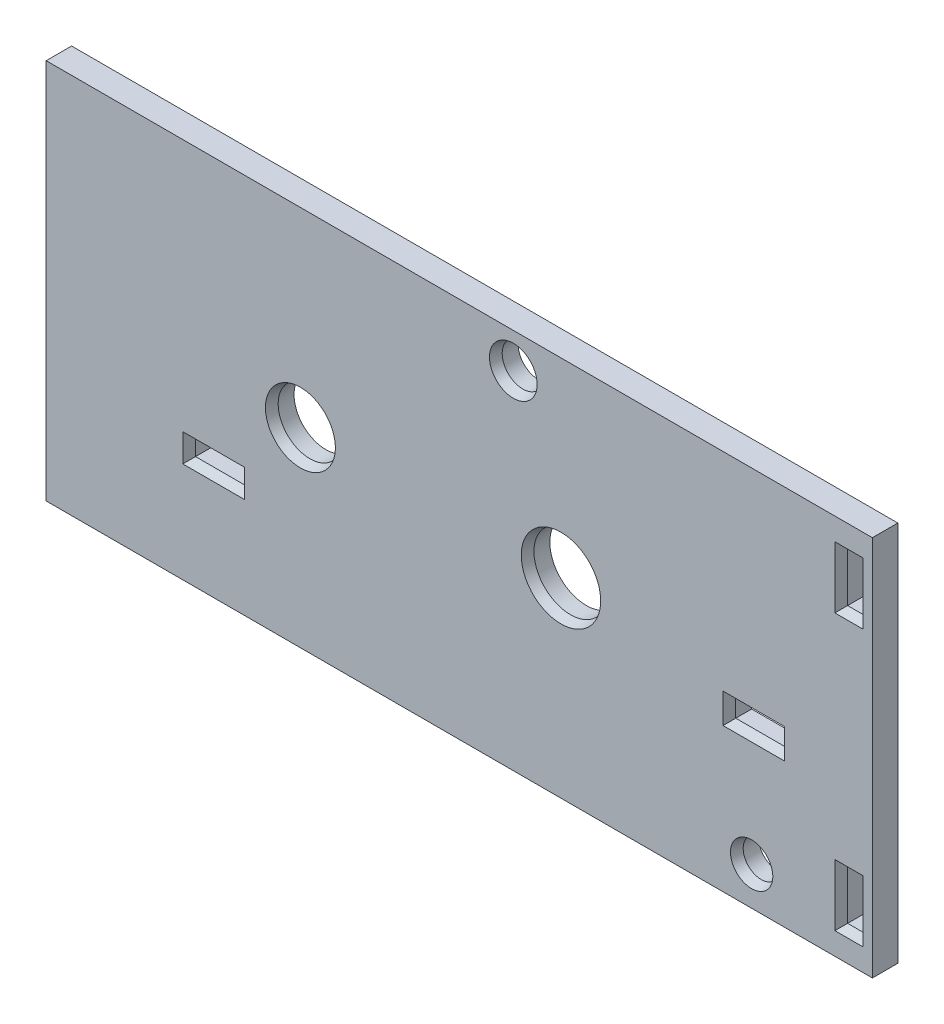
SolidWorks part; units mm, degrees
ref_plane "Front Plane" through (0, 0, 0) normal (0, 0, 1) x (1, 0, 0)
ref_plane "Top Plane" through (0, 0, 0) normal (0, 1, 0) x (1, 0, 0)
ref_plane "Right Plane" through (0, 0, 0) normal (1, 0, 0) x (0, 0, -1)
sketch "Sketch1" plane through (0, 0, 0) normal (0, 0, 1) x (1, 0, 0)
  line L0 (-55.3, -10.3) -> (-55.3, -13.7)
  line L1 (-86, -30) -> (44, -30)
  line L2 (-86, -30) -> (-86, 30)
  line L3 (-86, 30) -> (44, 30)
  line L4 (44, -30) -> (44, 30)
  line L5 (-64, -10.3) -> (-55.3, -10.3)
  line L6 (-64, -10.3) -> (-64, -13.7)
  line L7 (-64, -13.7) -> (-55.3, -13.7)
  line L13 (29.7, -5) -> (21, -5) construction
  line L14 (-55.3, -12) -> (-64, -12) construction
  line L15 (-59.65, -10.3) -> (-59.65, -13.7) construction
  line L16 (40.3, 26) -> (40.3, 17.3) construction
  line L17 (38.6, 26) -> (42, 26)
  line L18 (38.6, 26) -> (38.6, 17.3)
  line L19 (38.6, 17.3) -> (42, 17.3)
  line L20 (42, 26) -> (42, 17.3)
  line L21 (38.6, -17.3) -> (42, -17.3)
  line L22 (38.6, -17.3) -> (38.6, -26)
  line L23 (38.6, -26) -> (42, -26)
  line L24 (42, -17.3) -> (42, -26)
  line L25 (42, 21.65) -> (38.6, 21.65) construction
  line L26 (40.3, -17.3) -> (40.3, -26) construction
  line L27 (42, -21.65) -> (38.6, -21.65) construction
  line L28 (21, -3.15) -> (29.7, -3.15)
  line L29 (21, -3.15) -> (21, -6.85)
  line L30 (21, -6.85) -> (29.7, -6.85)
  line L31 (29.7, -3.15) -> (29.7, -6.85)
  line L32 (25.35, -6.85) -> (25.35, -3.15) construction
  circle A2 centre (-46, 0) radius 5
  circle A3 centre (-12.5, 24.5) radius 3.25
  circle A4 centre (25, -24) radius 2.83
  circle A5 centre (-5, 0) radius 5.75
  point P1 (0, 0)
  point P24 (-86, 0)
  dimension "D10" = 6.5
  dimension "D14" = 5.66
  dimension "D21" = 10
  dimension "D22" = 11.5
  dimension "D2" = 60
  dimension "D4" = 130
  dimension "D6" = 8.7
  dimension "D8" = 3.4
  dimension "D12" = 111
  dimension "D19" = 24.5
  dimension "D13" = 24
  dimension "D5" = 40
  dimension "D7" = 33.5
  dimension "D9" = 7.5
  dimension "D11" = 26.35
  dimension "D15" = 126.3
  dimension "D17" = 21.65
  dimension "D18" = 21.65
  dimension "D16" = 85
  dimension "D3" = 5
  dimension "D20" = 12
extrude "Boss-Extrude1" add sketch "Sketch1" along normal mid plane 4
sketch "Sketch2" plane through (0, 0, 2) normal (0, 0, 1) x (1, 0, 0)
  line L0 (40.3, 26) -> (40.3, 17.3) construction
  line L1 (42, 21.65) -> (38.6, 21.65) construction
  line L2 (40.3, -17.3) -> (40.3, -26) construction
  line L3 (42, -17.3) -> (38.6, -17.3) construction
  line L4 (38.6, -26) -> (42, -26) construction
  line L5 (38.6, -21.65) -> (42, -21.65) construction
  line L6 (38.6, -17.3) -> (38.6, -26) construction
  line L7 (42, -26) -> (42, -17.3) construction
sketch "Sketch4" plane through (0, 0, -2) normal (0, 0, -1) x (-1, 0, 0)
  line L0 (59.65, -10.3) -> (59.65, -13.7) construction
  line L1 (55.3, -12) -> (64, -12) construction
  line L2 (-29.7, -5) -> (-21, -5) construction
  line L3 (-29.7, -6.85) -> (-29.7, -3.15) construction
  line L4 (-21, -3.15) -> (-21, -6.85) construction
  line L5 (-25.35, -3.15) -> (-25.35, -6.85) construction
  line L6 (-29.7, -3.15) -> (-21, -3.15) construction
  line L7 (-21, -6.85) -> (-29.7, -6.85) construction
chamfer "Chamfer1" distance 0.5 distance2 1.5 20 edges at (40.3, -26, 2) (42, -21.65, 2) (40.3, -17.3, 2) (38.6, -21.65, 2) (0.75, 0, 2) (27.83, -24, 2) (-41, 0, 2) (-9.25, 24.5, 2) (-59.65, -13.7, 2) (-55.3, -12, 2) (-59.65, -10.3, 2) (-64, -12, 2) (25.35, -6.85, 2) (29.7, -5, 2) (25.35, -3.15, 2) (21, -5, 2) (40.3, 17.3, 2) (42, 21.65, 2) (40.3, 26, 2) (38.6, 21.65, 2) first distance on face at (40.3, 21.65, 2)
equation "\"padding\"=4"
equation "\"hole_width\"=3.4"
equation "\"hole_height\"=8.7"
equation "\"back_boost\"= 7"
equation "\"D5@Sketch1\"=33+\"back_boost\""
equation "\"D12@Sketch1\"=104+\"back_boost\""
equation "\"D15@Sketch1\"=119.30mm+\"back_boost\""
equation "\"D11@Sketch1\"=\"back_boost\"+19.35mm"
equation "\"D4@Sketch1\"=\"back_boost\"+123.00mm"
equation "\"pin_hole_height\"=9.2"
equation "\"pin_hole_width\"=3.53"
